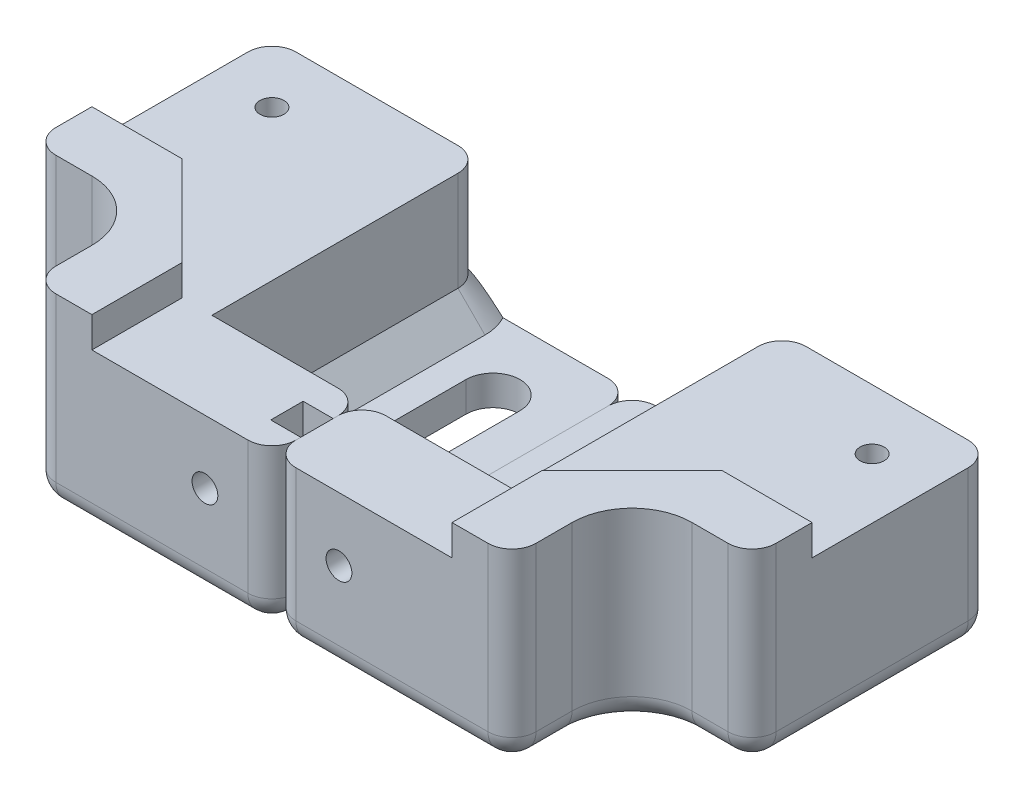
SolidWorks part; units mm, degrees
ref_plane "Front Plane" through (0, 0, 0) normal (0, 0, 1) x (1, 0, 0)
ref_plane "Top Plane" through (0, 0, 0) normal (0, 1, 0) x (1, 0, 0)
ref_plane "Right Plane" through (0, 0, 0) normal (1, 0, 0) x (0, 0, -1)
sketch "Sketch1" plane through (0, 0, 0) normal (0, 1, 0) x (1, 0, 0)
  line L0 (40, 0) -> (40, 20)
  line L1 (0, 0) -> (40, 0)
  line L2 (0, 0) -> (0, 60)
  line L3 (0, 60) -> (60, 60)
  line L4 (60, 20) -> (60, 60)
  line L5 (40, 20) -> (60, 20)
  line L6 (40, 10) -> (0, 10) construction
  line L7 (20, 10) -> (20, 0) construction
  line L8 (40, 20) -> (0, 60) construction
  line L9 (50, 20) -> (50, 60) construction
  line L10 (11.1668, 28) -> (11.1668, 48) construction
  line L17 (6.6668, 28) -> (6.6668, 48)
  line L18 (15.6668, 28) -> (15.6668, 48)
  circle A0 centre (35, 10) radius 2
  circle A2 centre (50, 25) radius 2
  circle A3 centre (50, 50) radius 2
  arc A4 (15.6668, 48) -> (6.6668, 48) centre (11.1668, 48) ccw
  arc A5 (6.6668, 28) -> (15.6668, 28) centre (11.1668, 28) ccw
  dimension "D4" = 4
  dimension "D5" = 10
  dimension "D7" = 9
  dimension "D1" = 40
  dimension "D2" = 60
  dimension "D3" = 5
  dimension "D6" = 11.1668
  dimension "D8" = 12
  dimension "D9" = 20
extrude "Boss-Extrude1" add sketch "Sketch1" along normal blind 26.1
sketch "Sketch2" plane through (0, 0, -60) normal (0, 0, -1) x (-1, 0, 0)
  line L0 (0, 26.1) -> (0, 0) construction
  line L1 (0, 5) -> (-25, 5)
  line L2 (0, 5) -> (0, 26.1)
  line L3 (0, 26.1) -> (-25, 26.1)
  line L4 (-25, 5) -> (-25, 26.1)
  line L6 (-60, 26.1) -> (0, 26.1) construction
  line L7 (-60, 0) -> (0, 0) construction
  dimension "D1" = 5
  dimension "D2" = 25
extrude "Cut-Extrude1" cut sketch "Sketch2" against normal blind 45
sketch "Sketch3" plane through (0, 26.1, 0) normal (0, 1, 0) x (1, 0, 0)
  line L0 (60, 30) -> (45, 30)
  line L1 (60, 20) -> (60, 60) construction
  line L2 (45, 30) -> (30, 15)
  line L3 (30, 15) -> (30, 0)
  line L4 (0, 0) -> (40, 0) construction
  line L5 (40, 0) -> (40, 20) construction
  line L6 (40, 20) -> (60, 20) construction
  line L7 (60, 30) -> (60, 20)
  line L8 (60, 20) -> (40, 20)
  line L9 (40, 20) -> (40, 0)
  line L10 (40, 0) -> (30, 0)
  dimension "D1" = 10
  dimension "D2" = 15
extrude "Boss-Extrude2" add sketch "Sketch3" along normal blind 5.1
fillet "Fillet1" radius 10 1 edges at (40, 15.6, -20)
sketch "Sketch4" plane through (0, 0, 0) normal (0, -1, 0) x (1, 0, 0)
  circle A0 centre (35, -10) radius 3.65
  circle A1 centre (50, -25) radius 3.65
  circle A2 centre (50, -50) radius 3.65
  dimension "D1" = 7.3
extrude "Cut-Extrude2" cut sketch "Sketch4" against normal blind 20
sketch "Sketch5" plane through (0, 0, 0) normal (0, 0, 1) x (1, 0, 0)
  line L0 (11.1668, 26.1) -> (11.1668, 5) construction
  line L1 (0, 26.1) -> (30, 26.1) construction
  line L2 (11.1668, 5) -> (0, 5) construction
  line L3 (0, 26.1) -> (0, 0) construction
  circle A0 centre (11.1668, 15.55) radius 2.15
  dimension "D3" = 4.3
  dimension "D1" = 21.1
  dimension "D2" = 11.1668
extrude "Cut-Extrude3" cut sketch "Sketch5" against normal blind 20
fillet "Fillet2" radius 4 14 edges at (40, 0, -5) (55, 0, -20) (60, 0, -40) (30, 0, -60) (0, 0, -30) (0, 15.55, -15) (25, 15.55, -60) (60, 13.05, -60) (0, 13.05, 0) (60, 15.6, -20) (40, 15.6, 0) (20, 0, 0) (42.9289, 0, -17.0711) (0, 2.5, -60)
chamfer "Chamfer1" distance 4.5 angle 45 4 edges at (26.1716, 5, -58.8284) (1.1716, 5, -13.8284) (25, 5, -35.5) (14.5, 5, -15)
mirror "Mirror1" about plane through (0, 26.1, 0) normal (1, 0, 0) of bodies 105
sketch "Sketch6" plane through (0, 0, 0) normal (1, 0, 0) x (0, 0, -1)
  line L0 (11, 26.1) -> (11, 9.5) construction
  line L1 (11, 17.8) -> (4, 17.8)
  line L2 (11, 17.8) -> (11, 21)
  line L3 (11, 21) -> (10.2, 21)
  line L4 (4, 17.8) -> (4, 21)
  line L5 (4, 4) -> (4, 26.1) construction
  line L6 (7.5, 17.8) -> (7.5, 26.1) construction
  line L7 (11, 26.1) -> (4, 26.1) construction
  line L8 (4.8, 21) -> (4, 21)
  line L10 (10.2, 21) -> (10.2, 26.1)
  line L11 (10.2, 26.1) -> (4.8, 26.1)
  line L12 (4.8, 21) -> (4.8, 26.1)
  point P16 (7.5, 26.1)
  dimension "D1" = 2.7
  dimension "D2" = 3.2
extrude "Cut-Extrude4" cut sketch "Sketch6" against normal blind 5
